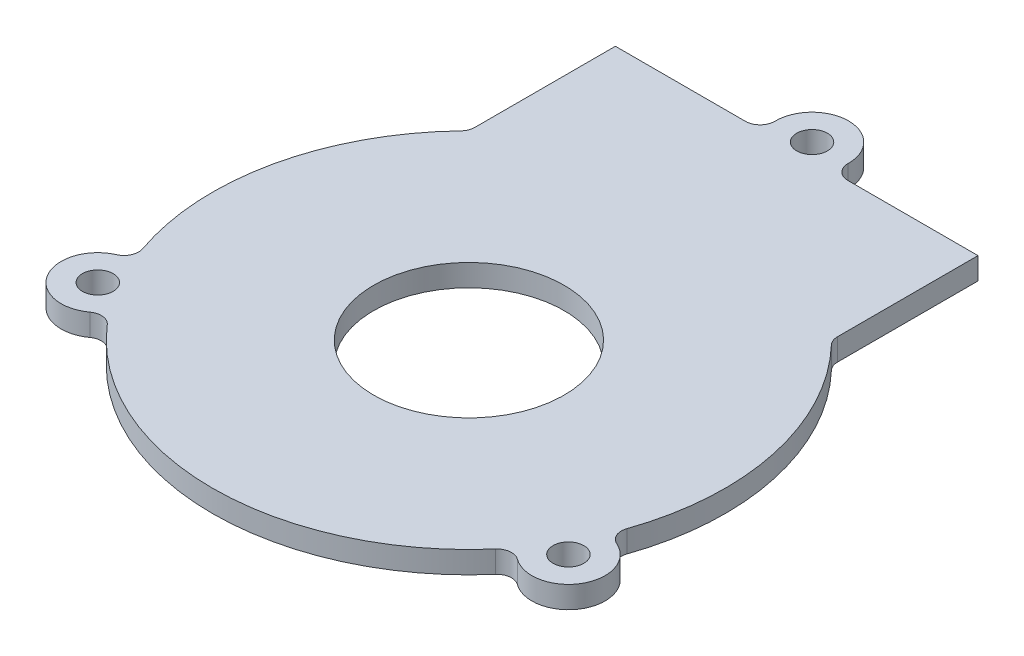
SolidWorks part; units mm, degrees
ref_plane "Front Plane" through (0, 0, 0) normal (0, 0, 1) x (1, 0, 0)
ref_plane "Top Plane" through (0, 0, 0) normal (0, 1, 0) x (1, 0, 0)
ref_plane "Right Plane" through (0, 0, 0) normal (1, 0, 0) x (0, 0, -1)
sketch "Sketch13" plane through (0, 0, 0) normal (0, 1, 0) x (1, 0, 0)
  circle A0 centre (0, 0) radius 35
extrude "Boss-Extrude3" add sketch "Sketch13" along normal blind 3
sketch "Sketch14" plane through (0, 3, 0) normal (0, 1, 0) x (1, 0, 0)
  line L0 (-24.7478, 24.7497) -> (24.7477, 24.7498)
  line L1 (-24.7478, 24.7497) -> (-24.7479, 44.7452)
  line L2 (24.7477, 24.7498) -> (24.7476, 44.7454)
  line L3 (-24.7479, 44.7452) -> (24.7476, 44.7454)
  line L4 (0, 0) -> (60.4611, -34.8658) construction
  line L5 (0, 0) -> (-56.6044, -32.6614) construction
  line L7 (-3.939, 44.1714) -> (-8.8985, 44.1714)
  line L8 (-3.939, 44.1714) -> (-3.939, 47.547)
  line L9 (-3.939, 47.547) -> (-8.8985, 47.547)
  line L10 (-8.8985, 44.1714) -> (-8.8985, 47.547)
  arc A0 (0, 35) -> (-24.7478, 24.7497) centre (0, 0) ccw construction
  circle A1 centre (0, 0) radius 35 construction
  arc A2 (0, 35) -> (-30.3109, -17.4999) centre (0, 0) ccw construction
  arc A3 (0, 35) -> (30.3118, -17.4984) centre (0, 0) ccw
  arc A4 (0, 35) -> (24.7477, 24.7498) centre (0, 0) ccw construction
  circle A5 centre (32.1365, -18.5413) radius 2.1017
  circle A6 centre (32.1365, -18.5413) radius 4.9951
  circle A7 centre (-32.1465, -18.5162) radius 2.0981
  circle A8 centre (-32.1465, -18.5162) radius 4.9995
extrude "Boss-Extrude4" add sketch "Sketch14" against normal up to surface (3 mm away) contours L0 L1 L3 L2 up to face at (0, 0, 35)
sketch "Sketch15" plane through (0, 3, 0) normal (0, 1, 0) x (1, 0, 0)
  line L0 (0, 0) -> (0, 62.3966) construction
  line L1 (-0.0001, 44.7453) -> (0, 46.8414) construction
  line L2 (-24.7479, 44.7452) -> (24.7476, 44.7454) construction
  circle A0 centre (0, 46.8414) radius 2.0961
  circle A1 centre (0, 46.8414) radius 4.996
extrude "Boss-Extrude11" add sketch "Sketch15" against normal up to surface (3 mm away) contours A1 | A0 up to face at (-0.0001, 0, -19.8101)
extrude "Boss-Extrude12" add sketch "Sketch14<6>" against normal up to surface (3 mm away) contours A6 up to face at (0, 0, -29.3038)
sketch "Sketch14<6>" plane through (0, 3, 0) normal (0, 1, 0) x (1, 0, 0) same geometry as "Sketch14"
extrude "Boss-Extrude14" add sketch "Sketch14<8>" against normal up to surface (3 mm away) contours L0 A5 region at (32.1365, 3, 18.5413) up to face at (5.9749, 0, -21.2696)
sketch "Sketch14<8>" plane through (0, 3, 0) normal (0, 1, 0) x (1, 0, 0) same geometry as "Sketch14"
hole_wizard "Ø4.2 (4.2) Diameter Hole1" positions "Sketch22" profile "Sketch23" hole size "Ø4.2" standard "ANSI Metric" end condition through all
sketch "Sketch22" plane through (0, 3, 0) normal (0, 1, 0) x (1, 0, 0)
  point P0 (32.1248, -18.5356)
sketch "Sketch23" plane through (32.1248, 3, 18.5356) normal (1, 0, 0) x (0, 0, 1)
  line L0 (0, 0) -> (0, 3)
  line L1 (0, 3) -> (2.1, 3)
  line L2 (2.1, 3) -> (2.1, 0)
  line L5 (2.1, 0) -> (0, 0)
  line L11 (0, -6.35) -> (0, 107.95) construction
  dimension "Thru Hole Dia." = 4.2
  dimension "Thru Hole Depth" = 3
extrude "Boss-Extrude15" add sketch "Sketch14<11>" against normal up to surface (3 mm away) contours A8 up to face at (32.1248, 0, 20.6356)
sketch "Sketch14<11>" plane through (0, 3, 0) normal (0, 1, 0) x (1, 0, 0) same geometry as "Sketch14"
hole_wizard "Ø4.2 (4.2) Diameter Hole2" positions "Sketch26" profile "Sketch27" hole size "Ø4.2" standard "ANSI Metric" end condition through all
sketch "Sketch26" plane through (0, 3, 0) normal (0, 1, 0) x (1, 0, 0)
  point P0 (-32.148, -18.5088)
  point P2 (-32.148, -18.5088)
sketch "Sketch27" plane through (-32.148, 3, 18.5088) normal (1, 0, 0) x (0, 0, 1)
  line L0 (0, 0) -> (0, 3)
  line L1 (0, 3) -> (2.1, 3)
  line L2 (2.1, 3) -> (2.1, 0)
  line L5 (2.1, 0) -> (0, 0)
  line L11 (0, -6.35) -> (0, 107.95) construction
  dimension "Thru Hole Dia." = 4.2
  dimension "Thru Hole Depth" = 3
fillet "Fillet4" radius 2 1 edges at (-24.7478, 1.5, -24.7497)
fillet "Fillet6" radius 2 1 edges at (-32.2839, 1.5, 13.5185)
fillet "Fillet7" radius 2 1 edges at (-27.8924, 1.5, 21.1427)
fillet "Fillet8" radius 2 1 edges at (27.8812, 1.5, 21.1574)
fillet "Fillet9" radius 2 1 edges at (32.2715, 1.5, 13.548)
fillet "Fillet10" radius 2 1 edges at (24.7477, 1.5, -24.7498)
fillet "Fillet11" radius 2 1 edges at (4.535, 1.5, -44.7453)
fillet "Fillet12" radius 2 1 edges at (-4.535, 1.5, -44.7453)
sketch "Sketch28" plane through (0, 3, 0) normal (0, 1, 0) x (1, 0, 0)
  circle A0 centre (0, 0) radius 5
extrude "Cut-Extrude1" cut sketch "Sketch28" against normal up to surface (3 mm away) up to face at (-32.148, 0, 20.6088)
sketch "Sketch29" plane through (0, 3, 0) normal (0, 1, 0) x (1, 0, 0)
  circle A0 centre (0, 0) radius 13
extrude "Cut-Extrude2" cut sketch "Sketch29" against normal up to surface (3 mm away) up to face at (0, 0, 5)
